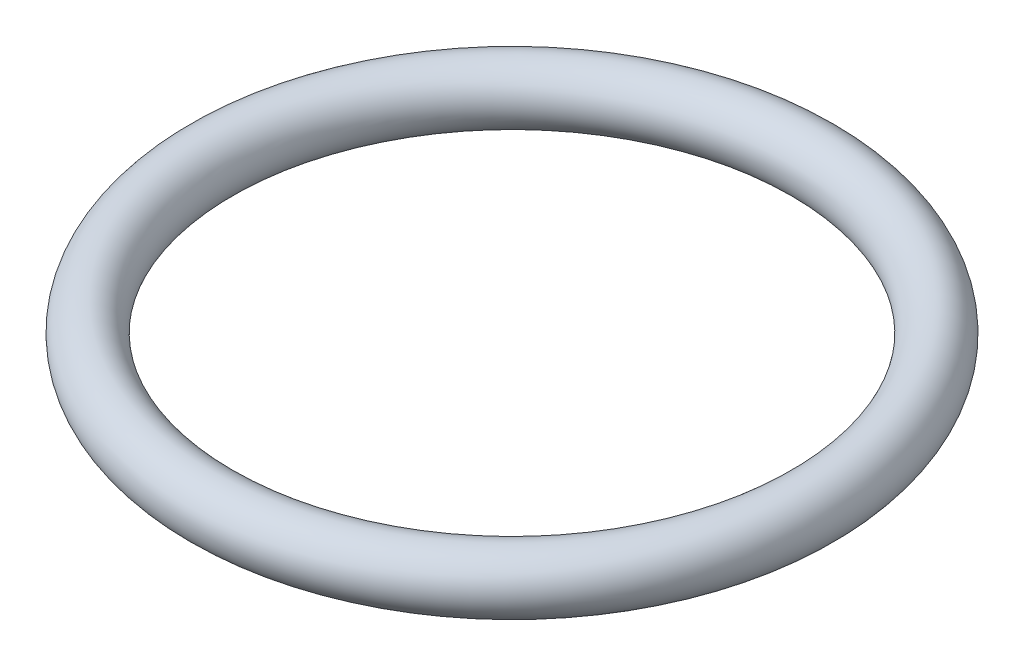
SolidWorks part; units mm, degrees
ref_plane "Front" through (0, 0, 0) normal (0, 0, 1) x (1, 0, 0)
ref_plane "Top" through (0, 0, 0) normal (0, 1, 0) x (1, 0, 0)
ref_plane "Right" through (0, 0, 0) normal (1, 0, 0) x (0, 0, -1)
sketch "Sketch1" plane through (0, 0, 0) normal (0, 0, 1) x (1, 0, 0)
  line L0 (0, 14.0803) -> (0, -13.5453) construction
  line L1 (-13.2918, 0) -> (15.7418, 0) construction
  circle A0 centre (-10.2, 0) radius 1
  dimension "D1" = 2
  dimension "D2" = 10.2
revolve "Revolve1" add sketch "Sketch1" angle 360 about L0
ref_axis "Axis1" through (0, 4.752, 0) along (0, -1, 0)
